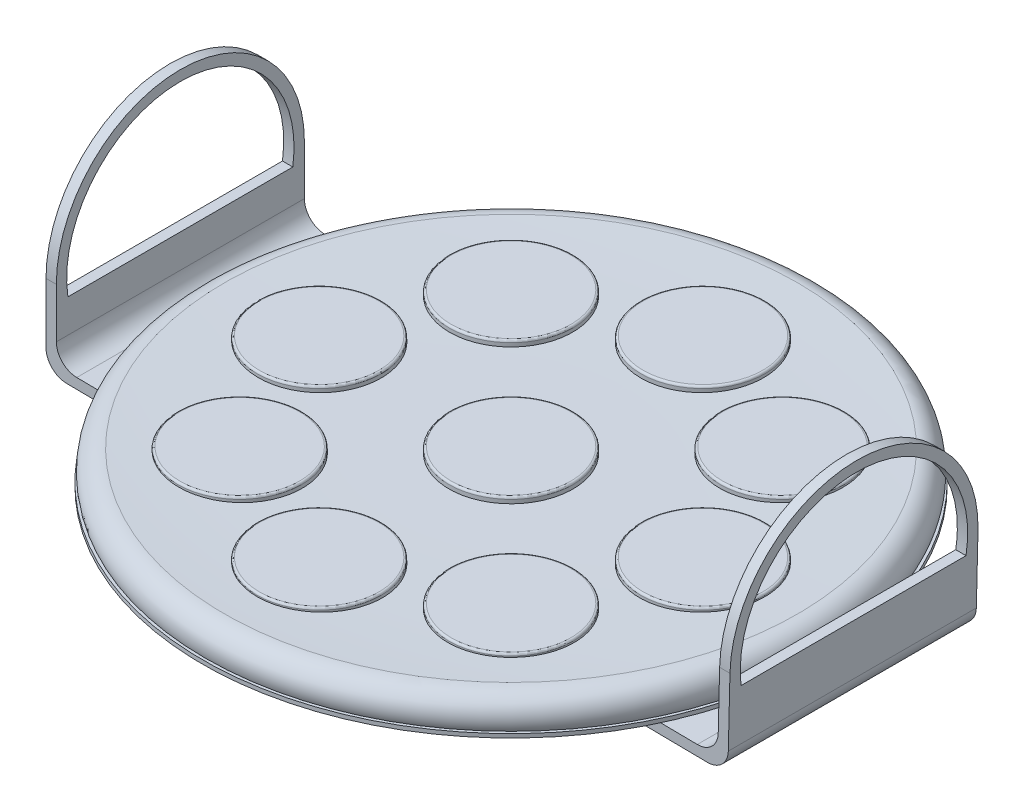
SolidWorks part; units mm, degrees
note: The reader was unsure of these and kept them because the rebuilt part matched: shared geometry of "Sketch1<5>".
ref_plane "Front Plane" through (0, 0, 0) normal (0, 0, 1) x (1, 0, 0)
ref_plane "Top Plane" through (0, 0, 0) normal (0, 1, 0) x (1, 0, 0)
ref_plane "Right Plane" through (0, 0, 0) normal (1, 0, 0) x (0, 0, -1)
sketch "Sketch1" plane through (0, 0, 0) normal (1, 0, 0) x (0, 0, -1)
  line L0 (0, -32.6278) -> (0, 15.1795) construction
  line L1 (128.6689, 0) -> (128.7718, 0)
  line L4 (0, -9.9) -> (84.3059, -9.9)
  line L5 (0, 3.1742) -> (149.2179, 3.1742)
  line L6 (149.2179, 3.1742) -> (149.2179, 1.3057)
  line L7 (0, 3.1742) -> (0, -9.9)
  line L8 (0, 3.1742) -> (0, 15.1795)
  line L9 (-32.3922, 15.1795) -> (32.3922, 15.1795) construction
  arc A0 (147.8808, 3.1742) -> (138.7179, 17.1795) centre (138.7179, 7.1795) ccw
  spline S0 degree 3 poles (84.3059, -9.9) (106.8929, -10.5442) (127.7915, -3.6655) (149.2179, 1.3057) knots 0 0 0 0 1 1 1 1
  spline S1 degree 2 poles (128.6689, 0) (128.7203, 0) (128.7718, 0) knots 0 0 0 0.004875 0.004875 0.004875
  spline S2 degree 3 poles (138.7179, 17.1795) (92.5242, 14.6866) (46.2976, 15.1795) (0, 15.1795) knots 0 0 0 0 1 1 1 1
  dimension "D1" = 20
revolve "Revolve2" add sketch "Sketch1" angle 360 about L0
revolve "Revolve3" add sketch "Sketch1<5>" angle 360 about L0
sketch "Sketch1<5>" plane through (0, 0, 0) normal (1, 0, 0) x (0, 0, -1) same geometry as "Sketch1"
sketch "Sketch5" plane through (0, 0, 0) normal (0, 0, 1) x (1, 0, 0)
  line L2 (-150.1093, 1.8172) -> (0, 0)
  line L9 (-160.2425, -3.0605) -> (-160.2425, 21.8793) construction
  line L10 (-155.1093, -3.1227) -> (-0.0606, -4.9996)
  line L16 (-160.2425, -3.0605) -> (-0.0606, -4.9996) construction
  line L17 (-155.2425, 1.8793) -> (-155.2425, 26.8793) construction
  line L18 (155.242, -1.8852) -> (0, 0) construction
  line L19 (155.1813, -6.8848) -> (-0.0606, -4.9996) construction
  line L20 (-155.2425, 1.8793) -> (0, 0) construction
  line L21 (-155.2425, 26.8793) -> (-205.2425, 26.8793) construction
  line L22 (-160.2425, 21.8793) -> (-205.2425, 21.8793) construction
  line L23 (0, 0) -> (-0.0606, -4.9996)
  line L24 (167.3628, 95.9071) -> (165.1065, 2.8743)
  line L25 (164.4122, 97.9793) -> (165.4119, 97.955)
  line L26 (160.2277, 7.9339) -> (162.3643, 96.0284)
  line L27 (154.988, -6.8825) -> (-0.0606, -4.9996)
  line L28 (150.1093, -1.8229) -> (0, 0)
  line L30 (-159.9883, 11.8164) -> (-159.9883, 99.9368)
  line L31 (-161.9883, 101.9368) -> (-162.9883, 101.9368)
  line L32 (-164.9883, 99.9368) -> (-164.9883, 6.8766)
  arc A10 (175.479, 17.6284) -> (155.242, -1.8852) centre (155.4849, 18.1133) cw construction
  arc A11 (180.4775, 17.5072) -> (155.1813, -6.8848) centre (155.4849, 18.1133) cw construction
  arc A13 (-159.9883, 11.8164) -> (-150.1093, 1.8172) centre (-149.9883, 11.8164) ccw
  arc A14 (-164.9883, 6.8766) -> (-155.1093, -3.1227) centre (-154.9883, 6.8766) ccw
  arc A15 (-159.9883, 99.9368) -> (-161.9883, 101.9368) centre (-161.9883, 99.9368) ccw
  arc A16 (-162.9883, 101.9368) -> (-164.9883, 99.9368) centre (-162.9883, 99.9368) ccw
  arc A17 (165.4119, 97.955) -> (167.3628, 95.9071) centre (165.3634, 95.9556) cw
  arc A18 (162.3643, 96.0284) -> (164.4122, 97.9793) centre (164.3637, 95.9799) cw
  arc A19 (165.1065, 2.8743) -> (154.988, -6.8825) centre (155.1094, 3.1168) cw
  arc A20 (160.2277, 7.9339) -> (150.1093, -1.8229) centre (150.2307, 8.1764) cw
  point P4 (0, 0)
  point P10 (0, 0)
  point P19 (-159.9883, 1.9368)
  point P25 (-159.9883, 101.9368)
  point P31 (-164.9883, 101.9368)
  point P44 (167.4113, 97.9065)
  point P45 (162.4128, 98.0278)
  point P46 (159.9882, -1.9428)
  dimension "D3" = 5
  dimension "D5" = 2
  dimension "D4" = 10
  dimension "D1" = 100
  dimension "D2" = 5
extrude "Boss-Extrude2" add sketch "Sketch5" along normal mid plane 120
sketch "Sketch6" plane through (0, 0, 0) normal (0, 1, 0) x (1, 0, 0)
  circle A0 centre (0, 92.8371) radius 30
  circle A1 centre (0, 0) radius 30
  circle A2 centre (65.6457, 65.6457) radius 30
  circle A3 centre (92.8371, 0) radius 30
  circle A4 centre (65.6457, -65.6457) radius 30
  circle A5 centre (0, -92.8371) radius 30
  circle A6 centre (-65.6457, -65.6457) radius 30
  circle A7 centre (-92.8371, 0) radius 30
  circle A8 centre (-65.6457, 65.6457) radius 30
  point P21 (0, 0)
  dimension "D1" = 60
  dimension "D2" = 8
extrude "Boss-Extrude4" add sketch "Sketch6" along normal blind 18
fillet "Fillet1" radius 1 9 edges at (-65.6457, 18, 95.6457) (0, 18, 122.8371) (65.6457, 18, 95.6457) (92.8371, 18, 30) (0, 18, 30) (65.6457, 18, -35.6457) (0, 18, -62.8371) (-65.6457, 18, -35.6457) (-92.8371, 18, 30)
sketch "Sketch7" plane through (0, 0, 0) normal (1, 0, 0) x (0, 0, -1)
  line L1 (-60, 35.9071) -> (-60, 101.9368)
  line L2 (-60, 101.9368) -> (60, 101.9368)
  line L3 (60, 101.9368) -> (60, 35.9071)
  line L5 (-60, 35.9071) -> (-60, 27.8743)
  line L6 (-60, 95.9071) -> (-60, 2.8743) construction
  line L7 (-60, 27.8743) -> (60, 27.8743)
  line L13 (60, 95.9071) -> (60, 2.8743) construction
  line L14 (60, 35.9071) -> (60, 27.8743)
  arc A1 (60, 35.9071) -> (-60, 35.9071) centre (0, 35.9071) ccw
  arc A2 (54.4102, 27.8743) -> (-54.4102, 27.8743) centre (0, 35.9071) ccw
  circle A3 centre (0, 35.9071) radius 60 construction
  circle A4 centre (0, 35.9071) radius 55 construction
  dimension "D2" = 5
extrude "Cut-Extrude3" cut sketch "Sketch7" against normal through all both and the other way through all contours A1 L3 L2 L1 | L7 A2
